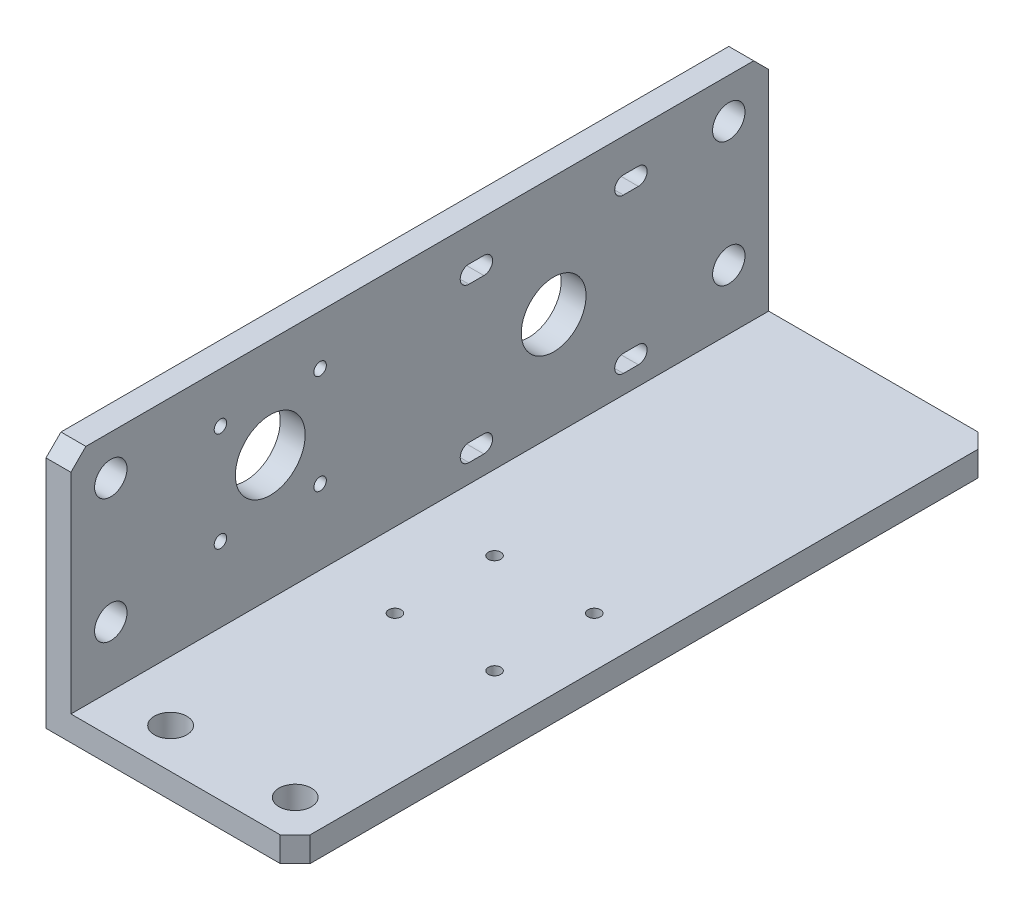
SolidWorks part; units mm, degrees
material "Lega 1060"
ref_plane "Piano frontale" through (0, 0, 0) normal (0, 0, 1) x (1, 0, 0)
ref_plane "Piano superiore" through (0, 0, 0) normal (0, 1, 0) x (1, 0, 0)
ref_plane "Piano destro" through (0, 0, 0) normal (1, 0, 0) x (0, 0, -1)
sketch "Schizzo1" plane through (0, 0, 0) normal (0, 0, 1) x (1, 0, 0)
  line L0 (0, 0) -> (0, 50)
  line L1 (0, 50) -> (5, 50)
  line L2 (5, 50) -> (5, 5)
  line L3 (5, 5) -> (50, 5)
  line L4 (50, 5) -> (50, 0)
  line L5 (50, 0) -> (0, 0)
  dimension "D1" = 5
  dimension "D2" = 5
  dimension "D3" = 50
  dimension "D4" = 50
extrude "Estrusione-Estrusione1" add sketch "Schizzo1" along normal blind 140
sketch "Schizzo2" plane through (0, 0, 0) normal (0, -1, 0) x (1, 0, 0)
  line L0 (5.4524, 132) -> (42.7933, 132) construction
  line L1 (0, 140) -> (50, 140) construction
  line L5 (50, 140) -> (50, 0) construction
  point P4 (17, 132)
  point P5 (42, 132)
  dimension "D1" = 8
  dimension "D2" = 25
  dimension "D3" = 8
sketch "Schizzo3" plane through (0, 0, 0) normal (-1, 0, 0) x (0, 0, 1)
  line L0 (132, 44.621) -> (132, 5.772) construction
  line L1 (140, 50) -> (140, 0) construction
  line L2 (140, 50) -> (0, 50) construction
  point P4 (132, 42)
  point P5 (132, 17)
  dimension "D1" = 8
  dimension "D2" = 8
  dimension "D3" = 25
hole_wizard "Foro Ø6.5 (6.5)-1" positions "Schizzo5" profile "Schizzo4" hole size "Ø6.5" standard "ISO" end condition through all
sketch "Schizzo5" plane through (0, 0, 0) normal (0, -1, 0) x (-1, 0, 0)
  point P0 (-17, -132)
  point P3 (-42, -132)
sketch "Schizzo4" plane through (17, 0, 132) normal (1, 0, 0) x (0, 0, -1)
  line L0 (0, 0) -> (0, 50)
  line L1 (0, 50) -> (3.25, 50)
  line L2 (3.25, 50) -> (3.25, 0)
  line L5 (3.25, 0) -> (0, 0)
  line L11 (0, -6.35) -> (0, 107.95) construction
  dimension "Thru Hole Dia." = 6.5
  dimension "Thru Hole Depth" = 50
hole_wizard "Foro Ø6.5 (6.5)-2" positions "Schizzo7" profile "Schizzo6" hole size "Ø6.5" standard "ISO"
sketch "Schizzo7" plane through (0, 0, 0) normal (-1, 0, 0) x (0, 0, 1)
  point P1 (132, 42)
  point P4 (132, 17)
sketch "Schizzo6" plane through (0, 42, 132) normal (0, 1, 0) x (0, 0, 1)
  line L0 (0, 0) -> (0, 6.9528)
  line L1 (0, 6.9528) -> (3.25, 5)
  line L2 (3.25, 5) -> (3.25, 0)
  line L5 (3.25, 0) -> (0, 0)
  line L10 (0, 6.9528) -> (-3.25, 5) construction
  line L11 (0, -6.35) -> (0, 107.95) construction
  dimension "Hole Dia." = 6.5
  dimension "Hole Depth" = 5
  dimension "Drill Angle" = 118
ref_plane "Piano1" through (0, 0, 70) normal (0, 0, 1) x (1, 0, 0)
mirror "Specchia1" about plane through (0, 0, 70) normal (0, 0, 1) of "Foro Ø6.5 (6.5)-2"
sketch "Schizzo8" plane through (0, 0, 0) normal (0, -1, 0) x (1, 0, 0)
  line L0 (30, 80) -> (7.0316, 80) construction
  line L1 (30, 80) -> (-7.1051, 42.8949) construction
  line L2 (0, 140) -> (50, 140) construction
  line L3 (50, 140) -> (50, 0) construction
  circle A0 centre (20, 70) radius 1.75
  circle A1 centre (20, 90) radius 1.75
  circle A2 centre (40, 90) radius 1.75
  circle A3 centre (40, 70) radius 1.75
  point P18 (30, 80)
  dimension "D3" = 3.5
  dimension "D1" = 60
  dimension "D2" = 20
  dimension "D4" = 45
  dimension "D5" = 20
  dimension "D6" = 4
sketch "Schizzo9" plane through (0, 0, 0) normal (-1, 0, 0) x (0, 0, 1)
  line L2 (140, 50) -> (0, 50) construction
  line L3 (140, 50) -> (140, 0) construction
  circle A4 centre (100, 30) radius 7
  point P18 (100, 30)
  dimension "D7" = 14
  dimension "D1" = 20
  dimension "D2" = 40
extrude "Taglio-Estrusione2" cut sketch "Schizzo9" against normal up to next
sketch "Schizzo11" plane through (0, 0, 0) normal (-1, 0, 0) x (0, 0, 1)
  line L0 (21.2202, 26) -> (65.0608, 26) construction
  line L1 (60.1405, 10.5) -> (57.1405, 10.5) construction
  line L2 (140, 0) -> (0, 0) construction
  line L3 (60.1405, 41.5) -> (57.1405, 41.5) construction
  line L4 (60.1405, 39.75) -> (57.1405, 39.75)
  line L5 (60.1405, 43.25) -> (57.1405, 43.25)
  line L6 (43.1405, 26) -> (43.1405, 48.418) construction
  line L7 (60.1405, 12.25) -> (57.1405, 12.25)
  line L8 (60.1405, 8.75) -> (57.1405, 8.75)
  line L9 (26.1405, 10.5) -> (29.1405, 10.5) construction
  line L10 (26.1405, 12.25) -> (29.1405, 12.25)
  line L11 (26.1405, 8.75) -> (29.1405, 8.75)
  line L12 (26.1405, 41.5) -> (29.1405, 41.5) construction
  line L13 (26.1405, 39.75) -> (29.1405, 39.75)
  line L14 (26.1405, 43.25) -> (29.1405, 43.25)
  circle A0 centre (43.1405, 26) radius 6.5
  arc A1 (60.1405, 39.75) -> (60.1405, 43.25) centre (60.1405, 41.5) ccw
  arc A2 (60.1405, 12.25) -> (60.1405, 8.75) centre (60.1405, 10.5) cw
  arc A3 (57.1405, 8.75) -> (57.1405, 12.25) centre (57.1405, 10.5) cw
  arc A4 (26.1405, 12.25) -> (26.1405, 8.75) centre (26.1405, 10.5) ccw
  arc A5 (29.1405, 8.75) -> (29.1405, 12.25) centre (29.1405, 10.5) ccw
  circle A6 centre (43.1405, 26) radius 21.9203 construction
  arc A7 (57.1405, 43.25) -> (57.1405, 39.75) centre (57.1405, 41.5) ccw
  arc A8 (26.1405, 39.75) -> (26.1405, 43.25) centre (26.1405, 41.5) cw
  arc A9 (29.1405, 43.25) -> (29.1405, 39.75) centre (29.1405, 41.5) cw
  circle A10 centre (100, 30) radius 7 construction
  point P10 (58.6405, 10.5)
  point P13 (58.6405, 41.5)
  point P18 (27.6405, 10.5)
  point P20 (43.1405, 26)
  point P33 (27.6405, 41.5)
  dimension "D2" = 31
  dimension "D3" = 31
  dimension "D5" = 57
  dimension "D1" = 13
  dimension "D4" = 26
  dimension "D8" = 3.5
  dimension "D9" = 3
extrude "Taglio-Estrusione4" cut sketch "Schizzo11" against normal up to next
chamfer "Smusso1" distance 3 angle 45 4 edges at (50, 2.5, 0) (2.5, 50, 0) (2.5, 50, 140) (50, 2.5, 140)
sketch "Sketch4" plane through (0, 0, 0) normal (-1, 0, 0) x (0, 0, 1)
  line L0 (100, 30) -> (100, 45.3374) construction
  line L1 (100, 30) -> (85.4455, 44.5545) construction
  line L2 (100, 30) -> (85.4455, 30) construction
  point P3 (90, 40)
  point P5 (110, 40)
  point P6 (90, 20)
  point P8 (110, 20)
  dimension "D1" = 45
  dimension "D2" = 10
hole_wizard "M3 Tapped Hole1" positions "3DSketch3" profile "Sketch5" tap size "M3" standard "ISO" end condition through all
sketch3d "3DSketch3"
  point P0 (0, 40, 90)
  point P3 (0, 40, 110)
  point P6 (0, 20, 110)
  point P9 (0, 20, 90)
sketch "Sketch5" plane through (0, 40, 90) normal (0, 1, 0) x (0, 0, 1)
  line L0 (0, 0) -> (0, 50)
  line L1 (0, 50) -> (1.25, 50)
  line L2 (1.25, 50) -> (1.25, 0)
  line L5 (1.25, 0) -> (0, 0)
  line L11 (0, -6.35) -> (0, 107.95) construction
  dimension "Thru Tap Drill Dia." = 2.5
  dimension "Thru Tap Drill Depth" = 50
cosmetic thread "Cosmetic Thread1" parameters "D2"=3
cosmetic thread "Cosmetic Thread2" parameters "D2"=3
cosmetic thread "Cosmetic Thread3" parameters "D2"=3
cosmetic thread "Cosmetic Thread4" parameters "D2"=3
hole_wizard "M3 Tapped Hole2" positions "3DSketch4" profile "Sketch6" tap size "M3" standard "ISO" end condition through all
sketch3d "3DSketch4"
  point P0 (20, 0, 90)
  point P3 (40, 0, 90)
  point P6 (40, 0, 70)
  point P9 (20, 0, 70)
sketch "Sketch6" plane through (20, 0, 90) normal (1, 0, 0) x (0, 0, -1)
  line L0 (0, 0) -> (0, 50)
  line L1 (0, 50) -> (1.25, 50)
  line L2 (1.25, 50) -> (1.25, 0)
  line L5 (1.25, 0) -> (0, 0)
  line L11 (0, -6.35) -> (0, 107.95) construction
  dimension "Thru Tap Drill Dia." = 2.5
  dimension "Thru Tap Drill Depth" = 50
cosmetic thread "Cosmetic Thread5" parameters "D2"=3
cosmetic thread "Cosmetic Thread6" parameters "D2"=3
cosmetic thread "Cosmetic Thread7" parameters "D2"=3
cosmetic thread "Cosmetic Thread8" parameters "D2"=3
